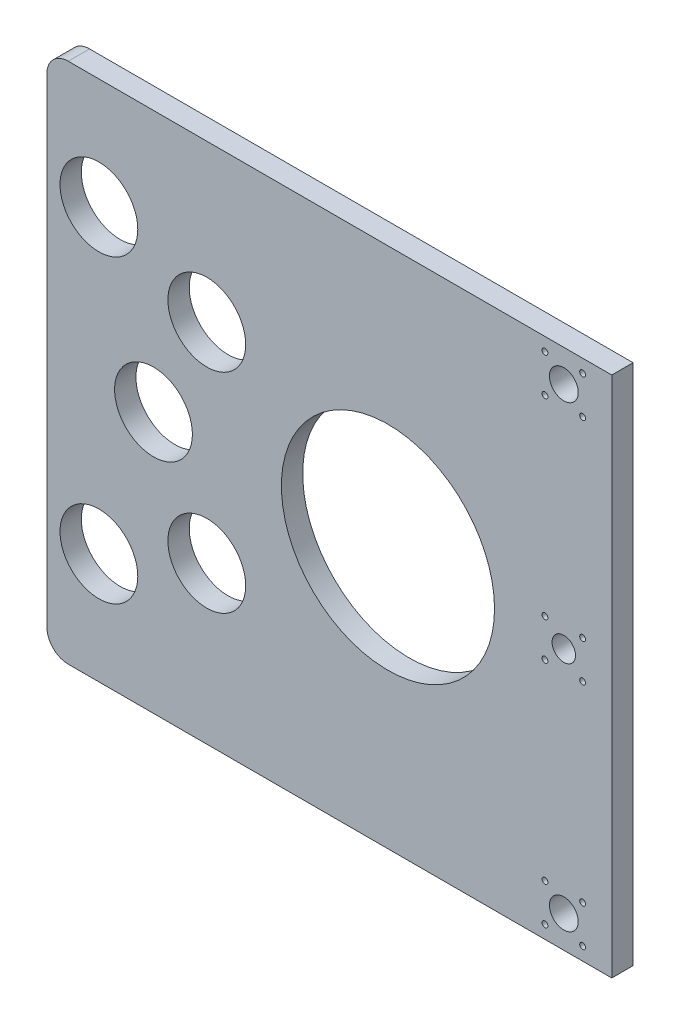
SolidWorks part; units mm, degrees
material "Органическое стекло СО-95-К ГОСТ 10667-90"
ref_plane "Спереди" through (0, 0, 0) normal (0, 0, 1) x (1, 0, 0)
ref_plane "Сверху" through (0, 0, 0) normal (0, 1, 0) x (1, 0, 0)
ref_plane "Справа" through (0, 0, 0) normal (1, 0, 0) x (0, 0, -1)
ref_axis "ОсьX" through (-88.99, 0, 0) along (1, 0, 0)
ref_axis "ОсьZ" through (0, 55, 0) along (0, -1, 0)
ref_axis "ОсьY" through (0, 0, -88.99) along (0, 0, 1)
sketch "Эскиз1" plane through (0, 0, 0) normal (0, 0, 1) x (1, 0, 0)
  line L0 (0, 0) -> (0, 59.9562) construction
  line L1 (-100, 245) -> (430, 245)
  line L2 (-100, 245) -> (-100, -245)
  line L3 (-100, -245) -> (430, -245)
  line L4 (430, 245) -> (430, -245)
  line L5 (367.3223, 17.6777) -> (385, 0) construction
  line L6 (-100, 245) -> (-100, -245)
  line L7 (430, 245) -> (430, -245)
  line L8 (-109.4093, 0) -> (189.9089, 0) construction
  line L9 (385, 0) -> (385, 25) construction
  line L10 (367.3223, 232.6777) -> (385, 215) construction
  line L11 (385, 215) -> (385, 240) construction
  circle A19 centre (0, 0) radius 36.5
  circle A20 centre (50, 97.9796) radius 36.5
  circle A21 centre (50, -97.9796) radius 36.5
  circle A22 centre (-51.2499, 140.9732) radius 36.5
  circle A23 centre (-51.2499, -140.9732) radius 36.5
  circle A24 centre (385, 0) radius 11
  circle A25 centre (385, 0) radius 25 construction
  circle A26 centre (367.3223, 17.6777) radius 2.75
  circle A27 centre (402.6777, 17.6777) radius 2.75
  circle A28 centre (367.3223, -17.6777) radius 2.75
  circle A29 centre (402.6777, -17.6777) radius 2.75
  circle A30 centre (385, 215) radius 13.5
  circle A32 centre (385, 215) radius 25 construction
  circle A33 centre (367.3223, 197.3223) radius 2.75
  circle A34 centre (402.6777, 197.3223) radius 2.75
  circle A35 centre (402.6777, 232.6777) radius 2.75
  circle A36 centre (367.3223, 232.6777) radius 2.75
  circle A37 centre (367.3223, -232.6777) radius 2.75
  circle A38 centre (402.6777, -232.6777) radius 2.75
  circle A39 centre (402.6777, -197.3223) radius 2.75
  circle A40 centre (367.3223, -197.3223) radius 2.75
  circle A41 centre (385, -215) radius 25 construction
  circle A42 centre (385, -215) radius 13.5
  point P6 (-100, 0)
  dimension "D3" = 430
  dimension "D4" = 27
  dimension "D5" = 45
  dimension "D6" = 73
  dimension "D8" = 50
  dimension "D13" = 22
  dimension "D14" = 50
  dimension "D15" = 5.5
  dimension "D18" = 5.5
  dimension "D19" = 50
  dimension "D1" = 530
  dimension "D2" = 490
  dimension "D7" = 430
  dimension "D9" = 110
  dimension "D10" = 110
  dimension "D11" = 150
  dimension "D12" = 45
  dimension "D16" = 45
extrude "Бобышка-Вытянуть1" add sketch "Эскиз1" along normal blind 20 contours L4 L1 L2 L3 region at (177.9351, 0, 0)
fillet "Скругление1" radius 20 2 edges at (-100, 245, 10) (-100, -245, 10)
sketch "Эскиз2" plane through (0, 0, 20) normal (0, 0, 1) x (1, 0, 0)
  circle A0 centre (220, 0) radius 100
  dimension "D2" = 200
  dimension "D1" = 220
extrude "Вырез-Вытянуть1" cut sketch "Эскиз2" against normal through all
